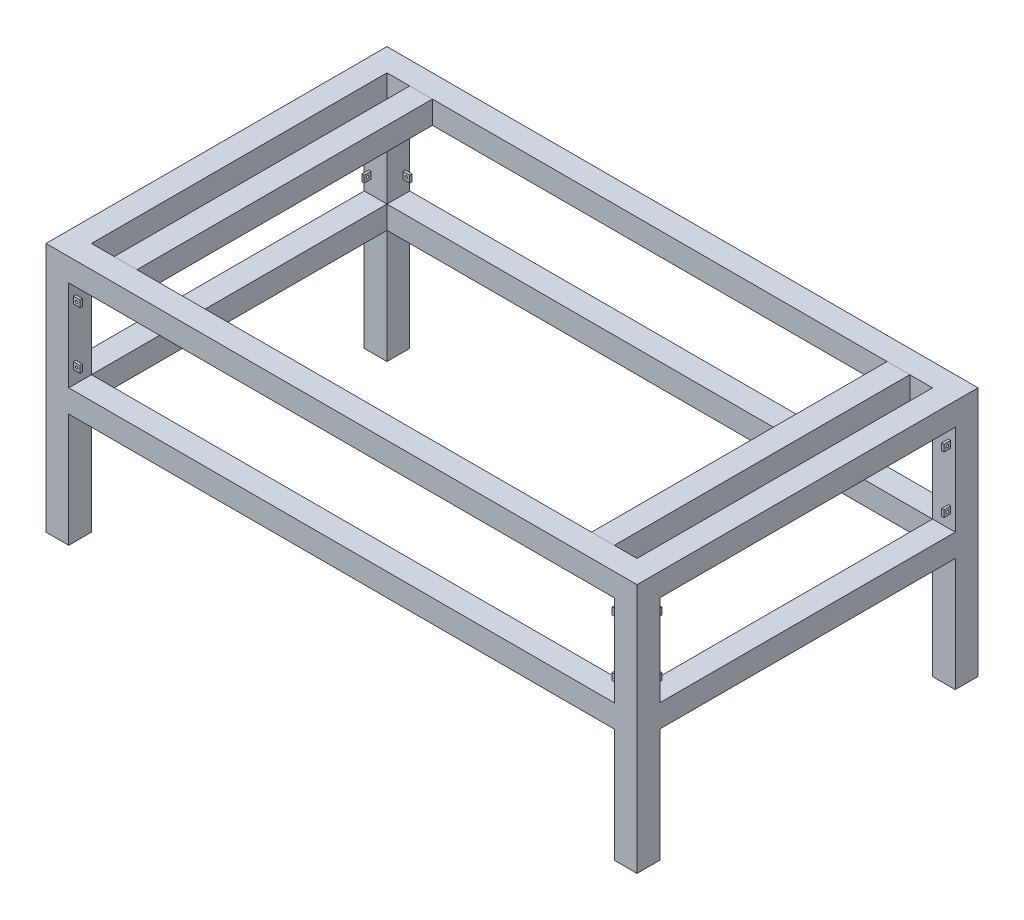
SolidWorks part; units mm, degrees
ref_plane "Plan de face" through (0, 0, 0) normal (0, 0, 1) x (1, 0, 0)
ref_plane "Plan de dessus" through (0, 0, 0) normal (0, 1, 0) x (1, 0, 0)
ref_plane "Plan de droite" through (0, 0, 0) normal (1, 0, 0) x (0, 0, -1)
sketch "Esquisse1" plane through (0, 0, 0) normal (0, 1, 0) x (1, 0, 0)
  line L1 (0, 0) -> (1300, 0)
  line L2 (0, 0) -> (0, 750)
  line L3 (0, 750) -> (1300, 750)
  line L4 (1300, 0) -> (1300, 750)
  line L5 (50, 700) -> (1250, 700)
  line L6 (50, 700) -> (50, 50)
  line L7 (50, 50) -> (1250, 50)
  line L8 (1250, 700) -> (1250, 50)
  dimension "D1" = 1300
  dimension "D2" = 750
  dimension "D3" = 50
  dimension "D4" = 50
  dimension "D5" = 50
  dimension "D6" = 50
extrude "Boss.-Extru.1" add sketch "Esquisse1" against normal blind 550
sketch "Esquisse2" plane through (0, 0, 0) normal (0, 0, 1) x (1, 0, 0)
  line L0 (0, 0) -> (1300, 0) construction
  line L1 (50, -50) -> (1250, -50)
  line L2 (50, -50) -> (50, -250)
  line L3 (50, -250) -> (1250, -250)
  line L4 (1250, -50) -> (1250, -250)
  line L5 (50, -300) -> (1250, -300)
  line L6 (50, -300) -> (50, -550)
  line L7 (50, -550) -> (1250, -550)
  line L8 (1250, -300) -> (1250, -550)
  line L9 (0, -550) -> (1300, -550) construction
  line L10 (1300, -550) -> (1300, 0) construction
  line L11 (0, -550) -> (0, 0) construction
  point P12 (1250, -425)
  dimension "D1" = 50
  dimension "D2" = 50
  dimension "D3" = 200
  dimension "D4" = 0
  dimension "D5" = 50
  dimension "D6" = 50
  dimension "D7" = 50
  dimension "D8" = 50
extrude "Enlèv. mat.-Extru.1" cut sketch "Esquisse2" against normal through all
sketch "Esquisse3" plane through (0, 0, 0) normal (-1, 0, 0) x (0, 0, 1)
  line L0 (-750, -550) -> (0, -550) construction
  line L1 (-700, -50) -> (-50, -50)
  line L2 (-700, -50) -> (-700, -250)
  line L3 (-700, -250) -> (-50, -250)
  line L4 (-50, -50) -> (-50, -250)
  line L5 (-700, -300) -> (-50, -300)
  line L6 (-700, -300) -> (-700, -550)
  line L7 (-700, -550) -> (-50, -550)
  line L8 (-50, -300) -> (-50, -550)
  line L9 (-750, 0) -> (0, 0) construction
  line L10 (0, -550) -> (0, 0) construction
  line L11 (-750, -550) -> (-750, 0) construction
  dimension "D1" = 50
  dimension "D2" = 50
  dimension "D3" = 50
  dimension "D4" = 50
  dimension "D5" = 50
  dimension "D6" = 200
  dimension "D7" = 50
extrude "Enlèv. mat.-Extru.2" cut sketch "Esquisse3" against normal through all
sketch "Esquisse4" plane through (0, 0, 0) normal (0, 1, 0) x (1, 0, 0)
  line L0 (1250, 700) -> (50, 700) construction
  line L1 (100, 700) -> (150, 700)
  line L2 (100, 700) -> (100, 50)
  line L3 (100, 50) -> (150, 50)
  line L4 (150, 700) -> (150, 50)
  line L5 (50, 50) -> (1250, 50) construction
  line L6 (50, 700) -> (50, 50) construction
  line L7 (1150, 700) -> (1200, 700)
  line L8 (1150, 700) -> (1150, 50)
  line L9 (1150, 50) -> (1200, 50)
  line L10 (1200, 700) -> (1200, 50)
  line L11 (1250, 50) -> (1250, 700) construction
  dimension "D1" = 50
  dimension "D2" = 50
  dimension "D3" = 50
  dimension "D4" = 50
extrude "Boss.-Extru.2" add sketch "Esquisse4" against normal blind 50 separate body
sketch "Esquisse5" plane through (1250, 0, 0) normal (-1, 0, 0) x (0, 0, 1)
  line L0 (-750, -250) -> (-750, -50) construction
  line L1 (-750, -80) -> (-735, -80)
  line L2 (-750, -80) -> (-750, -95)
  line L3 (-750, -95) -> (-735, -95)
  line L4 (-735, -80) -> (-735, -95)
  line L5 (-740, -80) -> (-740, -95)
  line L6 (-750, -205) -> (-735, -205)
  line L7 (-750, -205) -> (-750, -220)
  line L8 (-750, -220) -> (-735, -220)
  line L9 (-735, -205) -> (-735, -220)
  line L10 (-740, -205) -> (-740, -220)
  line L11 (-750, -50) -> (-700, -50) construction
  line L12 (-750, -250) -> (-700, -250) construction
  dimension "D1" = 10
  dimension "D2" = 5
  dimension "D3" = 5
  dimension "D4" = 15
  dimension "D5" = 15
  dimension "D6" = 30
  dimension "D7" = 30
extrude "Boss.-Extru.3" add sketch "Esquisse5" along normal blind 15 contours L1 L5 L3 L4 | L6 L10 L8 L9 region at (1250, -87.5, -737.5) region at (1250, -212.5, -737.5)
sketch "Esquisse6" plane through (0, 0, -700) normal (0, 0, 1) x (1, 0, 0)
  line L0 (1300, -50) -> (1300, -250) construction
  line L1 (1300, -80) -> (1285, -80)
  line L2 (1300, -80) -> (1300, -95)
  line L3 (1300, -95) -> (1285, -95)
  line L4 (1285, -80) -> (1285, -95)
  line L5 (1290, -80) -> (1290, -95)
  line L6 (1300, -220) -> (1285, -220)
  line L7 (1300, -220) -> (1300, -205)
  line L8 (1300, -205) -> (1285, -205)
  line L9 (1285, -220) -> (1285, -205)
  line L10 (1290, -205) -> (1290, -220)
  line L11 (1300, -50) -> (1250, -50) construction
  line L12 (1300, -250) -> (1250, -250) construction
  point P18 (1292.5, -220)
  dimension "D1" = 15
  dimension "D2" = 15
  dimension "D3" = 5
  dimension "D4" = 5
  dimension "D5" = 10
  dimension "D6" = 30
  dimension "D7" = 30
extrude "Boss.-Extru.4" add sketch "Esquisse6" along normal blind 15 contours L5 L1 L4 L3 | L10 L8 L9 L6 region at (1287.5, -87.5, -700) region at (1287.5, -212.5, -700)
sketch "Esquisse7" plane through (50, 0, 0) normal (1, 0, 0) x (0, 0, -1)
  line L0 (750, -50) -> (750, -250) construction
  line L1 (750, -80) -> (735, -80)
  line L2 (750, -80) -> (750, -95)
  line L3 (750, -95) -> (735, -95)
  line L4 (735, -80) -> (735, -95)
  line L5 (740, -80) -> (740, -95)
  line L6 (750, -220) -> (735, -220)
  line L7 (750, -220) -> (750, -205)
  line L8 (750, -205) -> (735, -205)
  line L9 (735, -220) -> (735, -205)
  line L10 (740, -205) -> (740, -220)
  line L11 (750, -250) -> (700, -250) construction
  line L12 (750, -50) -> (700, -50) construction
  dimension "D1" = 15
  dimension "D2" = 15
  dimension "D3" = 10
  dimension "D4" = 5
  dimension "D5" = 5
  dimension "D6" = 30
  dimension "D7" = 30
extrude "Boss.-Extru.5" add sketch "Esquisse7" along normal blind 15 contours L5 L1 L4 L3 | L10 L8 L9 L6 region at (50, -87.5, -737.5) region at (50, -212.5, -737.5)
sketch "Esquisse8" plane through (0, 0, -700) normal (0, 0, 1) x (1, 0, 0)
  line L0 (0, -50) -> (0, -250) construction
  line L1 (10, -80) -> (10, -95)
  line L2 (0, -80) -> (15, -80)
  line L3 (0, -80) -> (0, -95)
  line L4 (0, -95) -> (15, -95)
  line L5 (15, -80) -> (15, -95)
  line L6 (0, -205) -> (15, -205)
  line L7 (0, -205) -> (0, -220)
  line L8 (0, -220) -> (15, -220)
  line L9 (15, -205) -> (15, -220)
  line L10 (10, -205) -> (10, -220)
  line L11 (50, -250) -> (0, -250) construction
  line L13 (50, -50) -> (0, -50) construction
  point P16 (7.5, -220)
  dimension "D1" = 15
  dimension "D2" = 5
  dimension "D3" = 10
  dimension "D4" = 30
  dimension "D5" = 5
  dimension "D6" = 10
  dimension "D7" = 15
  dimension "D8" = 30
extrude "Boss.-Extru.6" add sketch "Esquisse8" along normal blind 15 contours L5 L2 L1 L4 | L6 L10 L8 L9 region at (12.5, -87.5, -700) region at (12.5, -212.5, -700)
sketch "Esquisse10" plane through (50, 0, 0) normal (1, 0, 0) x (0, 0, -1)
  line L0 (0, -50) -> (0, -250) construction
  line L1 (0, -80) -> (15, -80)
  line L2 (0, -80) -> (0, -95)
  line L3 (0, -95) -> (15, -95)
  line L4 (15, -80) -> (15, -95)
  line L5 (10, -80) -> (10, -95)
  line L6 (0, -205) -> (15, -205)
  line L7 (0, -205) -> (0, -220)
  line L8 (0, -220) -> (15, -220)
  line L9 (15, -205) -> (15, -220)
  line L10 (10, -205) -> (10, -220)
  line L11 (50, -250) -> (0, -250) construction
  line L12 (50, -50) -> (0, -50) construction
  point P18 (7.5, -80)
  dimension "D1" = 5
  dimension "D2" = 5
  dimension "D3" = 15
  dimension "D4" = 15
  dimension "D5" = 15
  dimension "D6" = 15
  dimension "D7" = 30
  dimension "D8" = 30
extrude "Boss.-Extru.7" add sketch "Esquisse10" along normal blind 15 contours L1 L5 L3 L4 | L6 L10 L8 L9 region at (50, -87.5, -12.5) region at (50, -212.5, -12.5)
sketch "Esquisse12" plane through (0, 0, -50) normal (0, 0, -1) x (-1, 0, 0)
  line L0 (0, -250) -> (0, -50) construction
  line L1 (0, -80) -> (-15, -80)
  line L2 (0, -80) -> (0, -95)
  line L3 (0, -95) -> (-15, -95)
  line L4 (-15, -80) -> (-15, -95)
  line L5 (-10, -80) -> (-10, -95)
  line L6 (0, -205) -> (-15, -205)
  line L7 (0, -205) -> (0, -220)
  line L8 (0, -220) -> (-15, -220)
  line L9 (-15, -205) -> (-15, -220)
  line L10 (-10, -205) -> (-10, -220)
  line L11 (-50, -50) -> (0, -50) construction
  line L12 (-50, -250) -> (0, -250) construction
  point P14 (-15, -87.5)
  dimension "D1" = 15
  dimension "D2" = 15
  dimension "D3" = 15
  dimension "D4" = 15
  dimension "D5" = 5
  dimension "D6" = 5
  dimension "D7" = 30
  dimension "D8" = 30
extrude "Boss.-Extru.8" add sketch "Esquisse12" along normal blind 15 contours L5 L1 L4 L3 | L10 L6 L9 L8 region at (12.5, -87.5, -50) region at (12.5, -212.5, -50)
sketch "Esquisse14" plane through (1250, 0, 0) normal (-1, 0, 0) x (0, 0, 1)
  line L0 (0, -250) -> (0, -50) construction
  line L1 (0, -80) -> (-15, -80)
  line L2 (0, -80) -> (0, -95)
  line L3 (0, -95) -> (-15, -95)
  line L4 (-15, -80) -> (-15, -95)
  line L5 (-10, -80) -> (-10, -95)
  line L6 (0, -205) -> (-15, -205)
  line L7 (0, -205) -> (0, -220)
  line L8 (0, -220) -> (-15, -220)
  line L9 (-15, -205) -> (-15, -220)
  line L10 (-10, -205) -> (-10, -220)
  line L11 (-50, -250) -> (0, -250) construction
  line L12 (-50, -50) -> (0, -50) construction
  point P18 (-15, -87.5)
  dimension "D1" = 15
  dimension "D2" = 5
  dimension "D3" = 15
  dimension "D4" = 30
  dimension "D5" = 30
  dimension "D6" = 5
  dimension "D7" = 15
  dimension "D8" = 15
extrude "Boss.-Extru.9" add sketch "Esquisse14" along normal blind 15 contours L5 L1 L4 L3 | L10 L6 L9 L8 region at (1250, -87.5, -12.5) region at (1250, -212.5, -12.5)
sketch "Esquisse15" plane through (0, 0, -50) normal (0, 0, -1) x (-1, 0, 0)
  line L0 (-1300, -250) -> (-1300, -50) construction
  line L1 (-1300, -80) -> (-1285, -80)
  line L2 (-1300, -80) -> (-1300, -95)
  line L3 (-1300, -95) -> (-1285, -95)
  line L4 (-1285, -80) -> (-1285, -95)
  line L5 (-1290, -80) -> (-1290, -95)
  line L6 (-1300, -205) -> (-1285, -205)
  line L7 (-1300, -205) -> (-1300, -220)
  line L8 (-1300, -220) -> (-1285, -220)
  line L9 (-1285, -205) -> (-1285, -220)
  line L10 (-1290, -205) -> (-1290, -220)
  line L11 (-1300, -50) -> (-1250, -50) construction
  line L12 (-1300, -250) -> (-1250, -250) construction
  point P14 (-1285, -212.5)
  point P15 (-1300, -212.5)
  dimension "D1" = 15
  dimension "D2" = 15
  dimension "D3" = 15
  dimension "D4" = 5
  dimension "D5" = 15
  dimension "D6" = 30
  dimension "D7" = 30
extrude "Boss.-Extru.10" add sketch "Esquisse15" along normal blind 15 contours L6 L10 L8 L9 | L1 L5 L3 L4 region at (1287.5, -87.5, -50) region at (1287.5, -212.5, -50)
sketch "Esquisse16" plane through (1290, 0, 0) normal (1, 0, 0) x (0, 0, -1)
  line L0 (65, -95) -> (50, -95) construction
  line L1 (65, -80) -> (50, -80) construction
  line L2 (65, -80) -> (65, -95) construction
  line L3 (50, -80) -> (50, -95) construction
  line L4 (65, -205) -> (65, -220) construction
  line L5 (65, -220) -> (50, -220) construction
  line L6 (685, -80) -> (685, -95) construction
  line L7 (685, -80) -> (700, -80) construction
  line L8 (685, -205) -> (685, -220) construction
  line L9 (685, -205) -> (700, -205) construction
  circle A0 centre (57.5, -87.5) radius 2.75
  circle A1 centre (57.5, -212.5) radius 2.75
  circle A2 centre (692.5, -87.5) radius 2.75
  circle A3 centre (692.5, -212.5) radius 2.75
  dimension "D5" = 5.5
  dimension "D6" = 5.5
  dimension "D9" = 5.5
  dimension "D12" = 5.5
  dimension "D1" = 15
  dimension "D2" = 7.5
  dimension "D3" = 15
  dimension "D4" = 7.5
  dimension "D7" = 7.5
  dimension "D8" = 7.5
  dimension "D10" = 7.5
  dimension "D11" = 7.5
  dimension "D13" = 7.5
  dimension "D14" = 7.5
extrude "Enlèv. mat.-Extru.3" cut sketch "Esquisse16" against normal blind 1500
sketch "Esquisse17" plane through (0, 0, -10) normal (0, 0, 1) x (1, 0, 0)
  line L0 (65, -205) -> (50, -205) construction
  line L1 (65, -205) -> (65, -220) construction
  line L2 (65, -80) -> (50, -80) construction
  line L3 (65, -80) -> (65, -95) construction
  line L4 (1235, -80) -> (1235, -95) construction
  line L5 (1235, -95) -> (1250, -95) construction
  line L6 (1235, -205) -> (1250, -205) construction
  line L8 (1235, -205) -> (1235, -220) construction
  circle A0 centre (57.5, -87.5) radius 2.75
  circle A1 centre (57.5, -212.5) radius 2.75
  circle A2 centre (1242.5, -212.5) radius 2.75
  circle A3 centre (1242.5, -87.5) radius 2.75
  point P24 (1235, -210.758)
  dimension "D1" = 5.5
  dimension "D2" = 5.5
  dimension "D3" = 5.5
  dimension "D4" = 5.5
  dimension "D5" = 7.5
  dimension "D6" = 7.5
  dimension "D7" = 7.5
  dimension "D8" = 7.5
  dimension "D9" = 7.5
  dimension "D10" = 7.5
  dimension "D11" = 7.5
  dimension "D12" = 7.5
extrude "Enlèv. mat.-Extru.4" cut sketch "Esquisse17" against normal blind 1000
